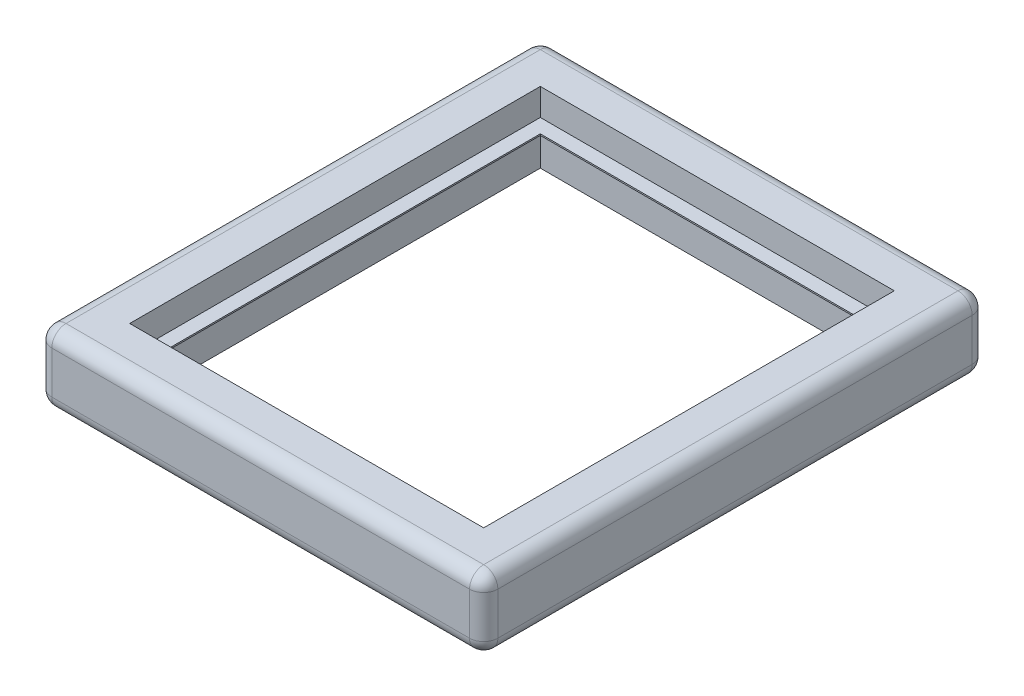
SolidWorks part; units mm, degrees
ref_plane "Front Plane" through (0, 0, 0) normal (0, 0, 1) x (1, 0, 0)
ref_plane "Top Plane" through (0, 0, 0) normal (0, 1, 0) x (1, 0, 0)
ref_plane "Right Plane" through (0, 0, 0) normal (1, 0, 0) x (0, 0, -1)
sketch "Sketch1" plane through (0, 0, 0) normal (0, 1, 0) x (1, 0, 0)
  line L0 (-400.05, 450.85) -> (400.05, 450.85)
  line L1 (-317.5, -368.3) -> (317.5, -368.3)
  line L2 (-317.5, -368.3) -> (-317.5, 368.3)
  line L3 (-317.5, 368.3) -> (317.5, 368.3)
  line L4 (317.5, -368.3) -> (317.5, 368.3)
  line L5 (-317.5, -368.3) -> (317.5, 368.3) construction
  line L6 (-317.5, 368.3) -> (317.5, -368.3) construction
  line L7 (400.05, -450.85) -> (400.05, 450.85)
  line L8 (-400.05, -450.85) -> (400.05, -450.85)
  line L9 (-400.05, -450.85) -> (-400.05, 450.85)
  line L10 (-292.1, 342.9) -> (292.1, 342.9)
  line L11 (292.1, -342.9) -> (292.1, 342.9)
  line L12 (-292.1, -342.9) -> (292.1, -342.9)
  line L13 (-292.1, -342.9) -> (-292.1, 342.9)
  point P0 (0, 0)
  dimension "D1" = 635
  dimension "D2" = 736.6
  dimension "D3" = 82.55
  dimension "D4" = 25.4
extrude "Boss-Extrude1" add sketch "Sketch1" along normal blind 50.8 and the other way blind 76.2 contours L9 L8 L7 L0 L4 L1 L2 L3 region at (0, 0, -438.795)
extrude "Boss-Extrude2" add sketch "Sketch1<3>" along normal blind 2.54 contours L1 L4 L3 L2 L12 L13 L10 L11 region at (-307.7748, 0, 0)
sketch "Sketch1<3>" plane through (0, 0, 0) normal (0, 1, 0) x (1, 0, 0) same geometry as "Sketch1"
fillet "Fillet1" radius 25.4 12 edges at (400.05, -76.2, 0) (400.05, -12.7, 450.85) (400.05, 50.8, 0) (400.05, -12.7, -450.85) (-400.05, -12.7, -450.85) (-400.05, -12.7, 450.85) (-400.05, -76.2, 0) (0, -76.2, -450.85) (0, -76.2, 450.85) (0, 50.8, 450.85) (0, 50.8, -450.85) (-400.05, 50.8, 0)
